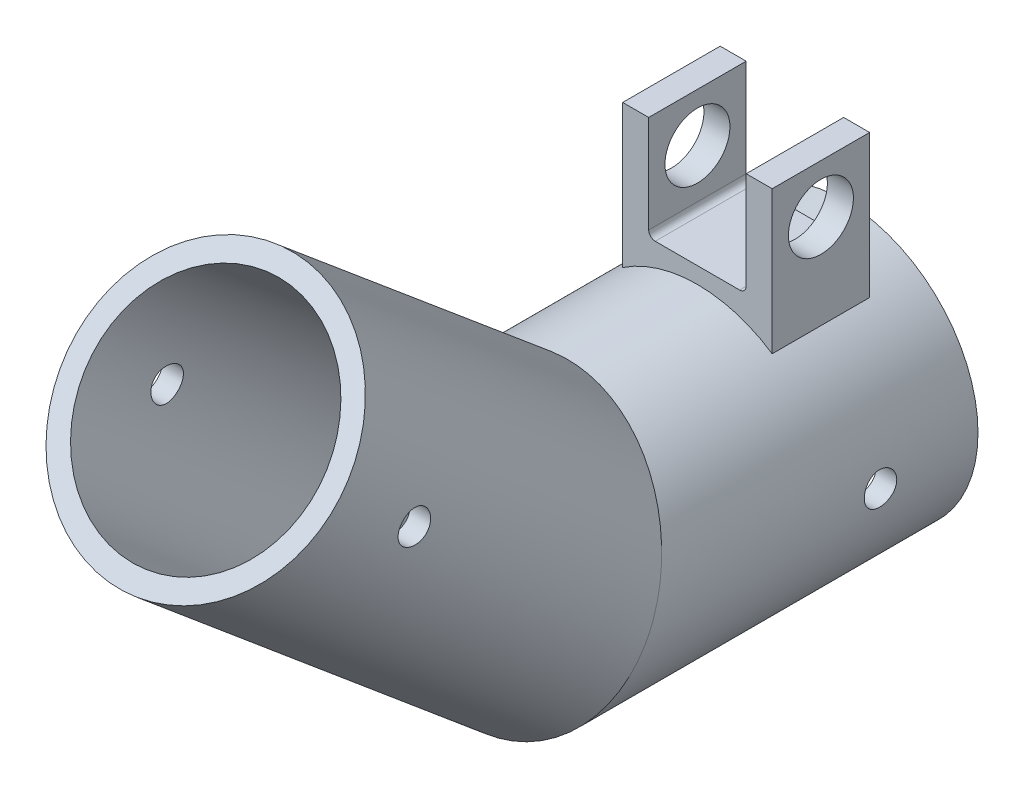
SolidWorks part; units mm, degrees
ref_plane "Front Plane" through (0, 0, 0) normal (0, 0, 1) x (1, 0, 0)
ref_plane "Top Plane" through (0, 0, 0) normal (0, 1, 0) x (1, 0, 0)
ref_plane "Right Plane" through (0, 0, 0) normal (1, 0, 0) x (0, 0, -1)
sketch "Sketch1" plane through (0, 0, 0) normal (0, 0, 1) x (1, 0, 0)
  circle A0 centre (0, 0) radius 20.675
  circle A1 centre (0, 0) radius 17.5
  dimension "D1" = 41.35
  dimension "D2" = 35
sketch "Sketch2" plane through (0, 0, 0) normal (1, 0, 0) x (0, 0, -1)
  line L0 (0, 0) -> (-50, 0)
  line L1 (-50, 0) -> (-98.1682, 40.4179)
  dimension "D1" = 50
  dimension "D2" = 140
sweep "Sweep1" add profiles "Sketch1" path "Sketch2"
sketch "Sketch3" plane through (0, 0, 0) normal (1, 0, 0) x (0, 0, -1)
  line L0 (0, 0) -> (-15, 0) construction
  line L1 (-98.1682, 40.4179) -> (-86.6776, 30.7761) construction
  line L2 (-84.8786, 56.2559) -> (-111.4579, 24.58) construction
  circle A0 centre (-86.6776, 30.7761) radius 2.5
  circle A1 centre (-15, 0) radius 2.5
  dimension "D3" = 5
  dimension "D1" = 15
  dimension "D2" = 15
extrude "Cut-Extrude1" cut sketch "Sketch3" against normal through all both and the other way through all
ref_plane "Plane1" through (0, 0, 15) normal (0, 0, -1) x (-1, 0, 0)
sketch "Sketch4" plane through (0, 0, 15) normal (0, 0, -1) x (-1, 0, 0)
  line L0 (0, 20.675) -> (0, 17.5) construction
  line L1 (-11.5, 39.1815) -> (-7.5, 39.1815)
  line L2 (-11.5, 39.1815) -> (-11.5, 17.1815)
  line L3 (-11.5, 17.1815) -> (-8.3143, 17.1815)
  line L4 (11.5, 39.1815) -> (11.5, 17.1815)
  line L5 (8.3143, 17.1815) -> (11.5, 17.1815)
  line L6 (7.5, 39.1815) -> (11.5, 39.1815)
  line L8 (-7.5, 39.1815) -> (-7.5, 24.1815)
  line L9 (-6.5, 23.1815) -> (6.5, 23.1815)
  line L10 (7.5, 39.1815) -> (7.5, 24.1815)
  circle A0 centre (0, 0) radius 20.675 construction
  circle A1 centre (0, 0) radius 20.675 construction
  arc A2 (8.3143, 17.1815) -> (-8.3143, 17.1815) centre (0, 0) ccw
  circle A3 centre (0, 0) radius 17.5 construction
  circle A4 centre (0, 0) radius 17.5 construction
  arc A5 (-6.5, 23.1815) -> (-7.5, 24.1815) centre (-6.5, 24.1815) cw
  arc A6 (7.5, 24.1815) -> (6.5, 23.1815) centre (6.5, 24.1815) cw
  point P9 (0, 23.1815)
  point P18 (0, 19.0875)
  dimension "D3" = 1
  dimension "D1" = 15
  dimension "D2" = 22
  dimension "D4" = 4
  dimension "D5" = 16
extrude "Boss-Extrude1" add sketch "Sketch4" along normal blind 7.5 and the other way blind 7.5
sketch "Sketch5" plane through (11.5, 0, 0) normal (1, 0, 0) x (0, 0, -1)
  line L1 (-15, -22.7425) -> (-15, 22.7425) construction
  line L2 (-22.5, 39.1815) -> (-7.5, 39.1815) construction
  circle A0 centre (-15, 31.6815) radius 5
  dimension "D1" = 10
  dimension "D2" = 7.5
extrude "Cut-Extrude2" cut sketch "Sketch5" against normal through all both and the other way through all
equation "\"tubeOutDiameter\" = 35mm"
equation "\"wheelShaftDiameter\"= 12mm"
equation "\"wheelThickness\"= 135mm"
equation "\"BearingDiameter\"= 20mm"
equation "\"BearingThickness\"= 10mm"
equation "\"D1@Sketch1\"=\"tubeOutDiameter\"+0.25in"
equation "\"D2@Sketch1\"=\"tubeOutDiameter\""
